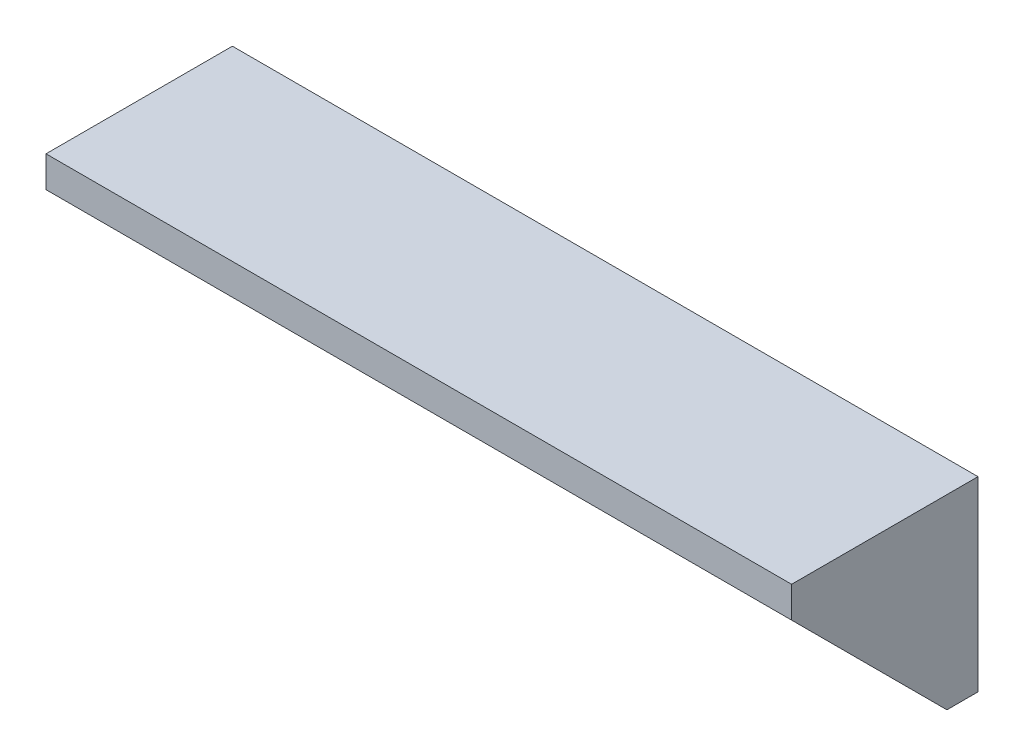
SolidWorks part; units mm, degrees
ref_plane "Front Plane" through (0, 0, 0) normal (0, 0, 1) x (1, 0, 0)
ref_plane "Top Plane" through (0, 0, 0) normal (0, 1, 0) x (1, 0, 0)
ref_plane "Right Plane" through (0, 0, 0) normal (1, 0, 0) x (0, 0, -1)
sketch "Sketch1" plane through (0, 0, 0) normal (0, 0, 1) x (1, 0, 0)
  line L0 (-60, 0) -> (-40, 0) construction
  line L1 (-60, 15) -> (60, 15)
  line L2 (-60, 15) -> (-60, -15)
  line L3 (-60, -15) -> (60, -15)
  line L4 (60, 15) -> (60, -15)
  line L5 (-60, 15) -> (60, -15) construction
  line L6 (-60, -15) -> (60, 15) construction
  line L7 (60, 0) -> (40, 0) construction
  circle A0 centre (-40, 0) radius 1.7
  circle A1 centre (40, 0) radius 1.7
  point P0 (0, 0)
extrude "Boss-Extrude1" add sketch "Sketch1" against normal blind 30
ref_plane "Plane1" through (0, 0, -25) normal (0, 0, -1) x (-1, 0, 0)
sketch "Sketch3" plane through (0, 0, -25) normal (0, 0, -1) x (-1, 0, 0)
  circle A0 centre (-40, 0) radius 3
  circle A1 centre (40, 0) radius 3
extrude "Cut-Extrude1" cut sketch "Sketch3" against normal blind 30
chamfer "Chamfer1" distance 25 angle 45 1 edges at (0, -15, 0)
